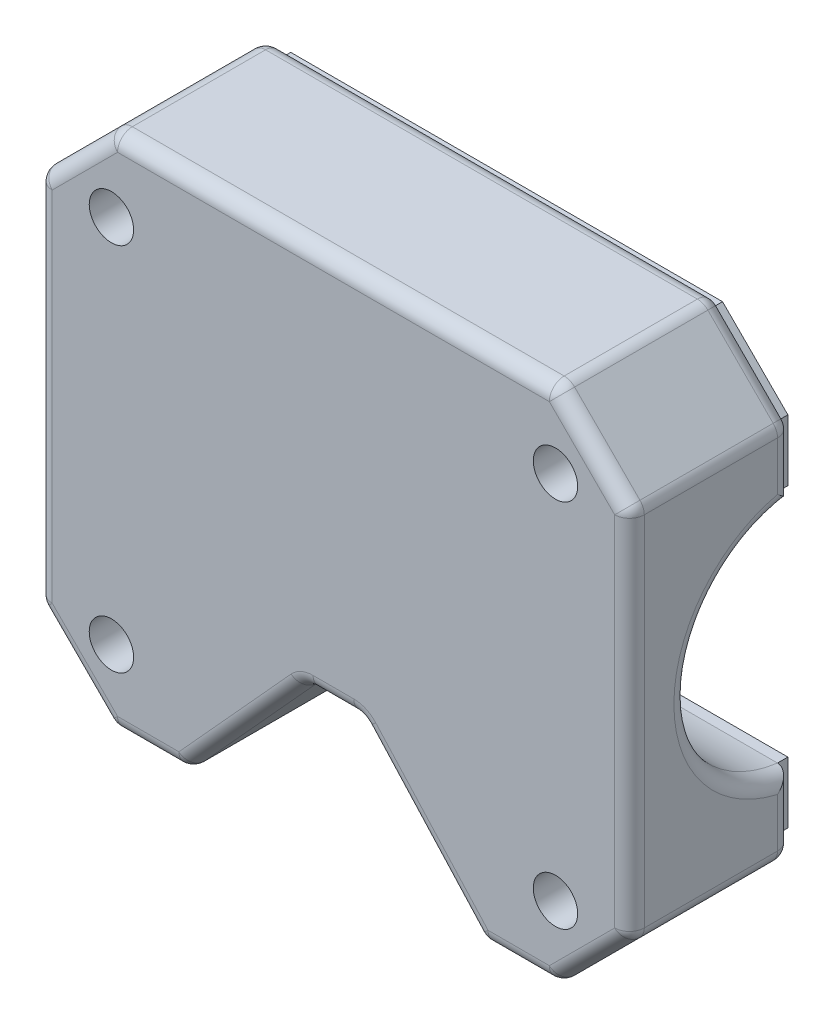
SolidWorks part; units mm, degrees
ref_plane "Front Plane" through (0, 0, 0) normal (0, 0, 1) x (1, 0, 0)
ref_plane "Top Plane" through (0, 0, 0) normal (0, 1, 0) x (1, 0, 0)
ref_plane "Right Plane" through (0, 0, 0) normal (1, 0, 0) x (0, 0, -1)
sketch "Sketch1" plane through (0, 0, 0) normal (0, 0, 1) x (1, 0, 0)
  line L1 (-20, -17.5) -> (20, -17.5)
  line L2 (-20, -17.5) -> (-20, 17.5)
  line L3 (-20, 17.5) -> (20, 17.5)
  line L4 (20, -17.5) -> (20, 17.5)
  line L5 (-20, -17.5) -> (20, 17.5) construction
  line L6 (-20, 17.5) -> (20, -17.5) construction
  line L7 (-15, -12.5) -> (15, -12.5) construction
  line L8 (-15, -12.5) -> (-15, 12.5) construction
  line L9 (-15, 12.5) -> (15, 12.5) construction
  line L10 (15, -12.5) -> (15, 12.5) construction
  line L11 (-15, -12.5) -> (15, 12.5) construction
  line L12 (-15, 12.5) -> (15, -12.5) construction
  circle A0 centre (0, 0) radius 8 construction
  circle A1 centre (-15, 12.5) radius 1.5
  circle A2 centre (15, 12.5) radius 1.5
  circle A3 centre (15, -12.5) radius 1.5
  circle A4 centre (-15, -12.5) radius 1.5
  dimension "D1" = 16
  dimension "D2" = 3
  dimension "D3" = 30
  dimension "D4" = 25
  dimension "D5" = 40
  dimension "D6" = 35
extrude "Boss-Extrude1" add sketch "Sketch1" along normal blind 12
sketch "Sketch2" plane through (-20, 0, 0) normal (-1, 0, 0) x (0, 0, 1)
  line L1 (1, 17.5) -> (1, -17.5)
  line L2 (1, 17.5) -> (1, -17.5)
  line L3 (1, 17.5) -> (1, -17.5)
  line L4 (1, 17.5) -> (29.851, 17.5)
  line L5 (1, -17.5) -> (29.851, -17.5)
  line L6 (29.851, 17.5) -> (29.851, -17.5)
  line L8 (1, 17.5) -> (0, 17.5)
  line L9 (1, 17.5) -> (1, -17.5)
  line L10 (1, -17.5) -> (0, -17.5)
  line L11 (0, 17.5) -> (0, -17.5)
  circle A0 centre (0, 0) radius 8
  line M5 (0, 17.5) -> (0, -17.5)
  line M6 (0, -17.5) -> (12, -17.5)
  line M8 (12, 17.5) -> (0, 17.5)
  dimension "D1" = 16
  dimension "D2" = 1
extrude "Cut-Extrude1" cut sketch "Sketch2" against normal blind 40 contours L9 A0 | L9 A0 L11 | A0 L1 M8 M5 | A0 L1 M5 M6 region at (-20, 12.7395, 0.5005) region at (-20, 0, 3.9418) region at (-20, 0, 0.4993) region at (-20, -12.7395, 0.5005)
sketch "Sketch5" plane through (0, 17.5, 0) normal (0, 1, 0) x (1, 0, 0)
  line L0 (-13.5, -4) -> (-13.5, -30.1703)
  line L1 (-13.5, -43.5797) -> (-13.5, -53)
  line L2 (-12.5, -54) -> (12.5, -54)
  line L3 (13.5, -53) -> (13.5, -43.5665)
  line L4 (13.5, -30.1671) -> (13.5, -4)
  line L5 (12.5, -3) -> (-12.5, -3)
  line L6 (0, -1) -> (0, -3)
  line L7 (20, -1) -> (-20, -1) construction
  line L8 (11, -53.75) -> (11, -36.875)
  line L9 (11, -36.875) -> (11, -20)
  line L10 (8, -17) -> (2.5, -17)
  line L11 (2.5, -17) -> (2.5, -12)
  line L12 (2.5, -12) -> (-2.5, -12)
  line L13 (-2.5, -12) -> (-2.5, -17)
  line L14 (-2.5, -17) -> (-8, -17)
  line L15 (-11, -20) -> (-11, -36.875)
  line L16 (-11, -36.875) -> (-11, -53.75)
  line L17 (-10.75, -54) -> (10.75, -54)
  circle A0 centre (-8.5, -48.5) radius 1.5
  arc A1 (-13.5, -53) -> (-12.5, -54) centre (-12.5, -53) ccw
  arc A2 (12.5, -54) -> (13.5, -53) centre (12.5, -53) ccw
  arc A3 (13.5, -4) -> (12.5, -3) centre (12.5, -4) ccw
  arc A4 (-12.5, -3) -> (-13.5, -4) centre (-12.5, -4) ccw
  circle A5 centre (8.5, -48.5) radius 1.5
  circle A6 centre (0, -14.5) radius 1.5
  circle A7 centre (0, -14.5) radius 1.5
  arc A8 (11, -20) -> (8, -17) centre (8, -20) ccw
  arc A9 (-8, -17) -> (-11, -20) centre (-8, -20) ccw
  arc A10 (-11, -53.75) -> (-10.75, -54) centre (-10.75, -53.75) ccw
  arc A11 (10.75, -54) -> (11, -53.75) centre (10.75, -53.75) ccw
  circle A12 centre (-8.5, -48.5) radius 1.5
  circle A13 centre (8.5, -48.5) radius 1.5
  spline S0 degree 3 poles (-13.5, -30.1703) (-13.5, -30.7241) (-13.4554, -31.2832) (-13.3208, -32.3903) (-13.2305, -32.9411) (-13.0479, -34.0426) (-12.9558, -34.5932) (-12.8189, -35.7001) (-12.7757, -36.2565) (-12.7724, -36.9579) (-12.7742, -37.1017) (-12.7828, -37.3864) (-12.7895, -37.5285) (-12.8164, -37.9539) (-12.8435, -38.2364) (-12.9441, -39.0815) (-13.037, -39.6418) (-13.2228, -40.7624) (-13.3155, -41.3227) (-13.454, -42.449) (-13.5, -43.016) (-13.5, -43.5797) knots 0 0 0 0 0.125 0.125 0.25 0.25 0.375 0.375 0.5 0.5 0.53125 0.53125 0.5625 0.5625 0.625 0.625 0.75 0.75 0.875 0.875 1 1 1 1
  spline S1 degree 3 poles (13.5, -43.5665) (13.5, -43.0131) (13.4554, -42.4545) (13.3209, -41.3482) (13.2307, -40.7978) (13.0482, -39.6971) (12.9562, -39.1469) (12.8195, -38.0409) (12.7762, -37.4849) (12.7729, -36.784) (12.7747, -36.6403) (12.7833, -36.3558) (12.79, -36.2138) (12.8169, -35.7887) (12.844, -35.5065) (12.9445, -34.662) (13.0373, -34.1021) (13.223, -32.9823) (13.3156, -32.4224) (13.454, -31.2969) (13.5, -30.7304) (13.5, -30.1671) knots 0 0 0 0 0.125 0.125 0.25 0.25 0.375 0.375 0.5 0.5 0.53125 0.53125 0.5625 0.5625 0.625 0.625 0.75 0.75 0.875 0.875 1 1 1 1
  point P28 (0, -3)
  dimension "D3" = 5
  dimension "D4" = 5.5
  dimension "D6" = 8.5
  dimension "D14" = 5.5
  dimension "D1" = 2
  dimension "D2" = 17
  dimension "D5" = 34
  dimension "D7" = 4.5
  dimension "D8" = 4
  dimension "D9" = 51
  dimension "D10" = 2.5
  dimension "D11" = 2.5
  dimension "D12" = 17
  dimension "D13" = 2.5
  dimension "D15" = 5.5
sketch "Sketch6" plane through (0, 17.5, 0) normal (0, 1, 0) x (1, 0, 0)
  line L0 (0, -1) -> (0, -3) construction
  line L1 (0, -1) -> (0, -3)
  line L2 (0, -13) -> (0, -16)
  line L3 (20.5345, -17) -> (11.5, -17)
  line L4 (3, -16.5) -> (3, -11.5)
  line L5 (3, -11.5) -> (-3, -11.5)
  line L6 (-20, -12) -> (20, -12)
  line L7 (20, -12) -> (20, -1)
  line L10 (-20, -12) -> (20, -12)
  line L11 (20, -12) -> (20, -1)
  line L12 (-3, -11.5) -> (-3, -16.5)
  line L13 (11.5, -12) -> (11.5, -36.875)
  line L14 (13.5, -30.1671) -> (13.5, -4)
  line L15 (13.5, -53) -> (13.5, -43.5665)
  line L16 (-12.5, -54) -> (12.5, -54)
  line L17 (-13.5, -43.5797) -> (-13.5, -53)
  line L18 (-13.5, -4) -> (-13.5, -30.1703)
  line L19 (12.5, -3) -> (-12.5, -3)
  line L20 (13.5, -30.1671) -> (13.5, -4)
  line L21 (13.5, -53) -> (13.5, -43.5665)
  line L22 (-12.5, -54) -> (12.5, -54)
  line L23 (-13.5, -43.5797) -> (-13.5, -53)
  line L24 (-13.5, -4) -> (-13.5, -30.1703)
  line L25 (12.5, -3) -> (-12.5, -3)
  line L26 (11.5, -36.875) -> (11.5, -16.5)
  line L27 (20.5345, -16.5) -> (2.5, -16.5)
  line L28 (20, -1) -> (-20, -1)
  line L29 (20, -1) -> (-20, -1)
  line L30 (-11, -36.875) -> (-11, -53.75)
  line L31 (-10.75, -54) -> (10.75, -54)
  line L32 (11, -53.75) -> (11, -36.875)
  line L33 (11, -36.875) -> (11, -20)
  line L34 (8, -17) -> (2.5, -17)
  line L35 (2.5, -17) -> (2.5, -12)
  line L36 (2.5, -12) -> (-2.5, -12)
  line L37 (-2.5, -12) -> (-2.5, -17)
  line L38 (-2.5, -17) -> (-8, -17)
  line L39 (-11, -20) -> (-11, -36.875)
  line L40 (-11, -36.875) -> (-11, -53.75) construction
  line L41 (-10.75, -54) -> (10.75, -54)
  line L42 (11, -53.75) -> (11, -36.875) construction
  line L43 (11, -36.875) -> (11, -17) construction
  line L44 (3, -17) -> (2.5, -17) construction
  line L45 (2.5, -16.5) -> (2.5, -12) construction
  line L46 (2.5, -12) -> (-2.5, -12) construction
  line L47 (-2.5, -12) -> (-2.5, -16.5) construction
  line L48 (-2.5, -17) -> (-3, -17) construction
  line L49 (-11, -17) -> (-11, -36.875) construction
  line L50 (-11.5, -16.5) -> (-11.5, -36.875)
  line L54 (-20, -1) -> (-20, -12)
  line L55 (-20, -1) -> (-20, -12)
  line L56 (-11.5, -36.875) -> (-11.5, -12)
  line L58 (-11.5, -17) -> (-11.5, -36.875) construction
  line L59 (11.5, -36.875) -> (11.5, -17) construction
  line L60 (8, -17) -> (3, -17) construction
  line L61 (3, -17) -> (2.5, -17) construction
  line L62 (20.5345, -17) -> (-20.5345, -17) construction
  line L63 (8, -17) -> (3, -17) construction
  line L64 (11, -17) -> (8, -17) construction
  line L65 (11.5, -17) -> (11, -17) construction
  line L66 (-8, -17) -> (-11, -17) construction
  line L67 (-11, -17) -> (-20.5345, -17)
  line L68 (-3, -17) -> (-8, -17) construction
  line L69 (-3, -17) -> (-8, -17) construction
  line L70 (-3, -16.5) -> (-3, -17) construction
  line L71 (-3, -11.5) -> (-3, -17) construction
  line L72 (-2.5, -16.5) -> (-2.5, -17) construction
  line L73 (-2.5, -12) -> (-2.5, -17) construction
  line L74 (0, -17) -> (-2.5, -17) construction
  line L75 (-2.5, -17) -> (-3, -17) construction
  line L76 (2.5, -17) -> (0, -17) construction
  line L77 (0, -16.5) -> (0, -17) construction
  line L78 (2.5, -17) -> (2.5, -16.5) construction
  line L79 (2.5, -17) -> (2.5, -12) construction
  line L80 (3, -17) -> (3, -16.5) construction
  line L81 (3, -17) -> (3, -11.5) construction
  line L82 (0, -16.5) -> (-2.5, -16.5) construction
  line L83 (-2.5, -16.5) -> (-20.5345, -16.5)
  line L84 (20.5345, -16.5) -> (-20.5345, -16.5) construction
  line L85 (2.5, -16.5) -> (0, -16.5) construction
  line L86 (0, -16) -> (0, -16.5) construction
  line L87 (-11.5, -36.875) -> (-11.5, -53.75) construction
  line L88 (11.5, -53.75) -> (11.5, -36.875) construction
  circle A1 centre (0, -14.5) radius 1.5
  circle A2 centre (0, -14.5) radius 1.5
  circle A3 centre (8.5, -48.5) radius 1.5
  circle A4 centre (8.5, -48.5) radius 1.5
  circle A5 centre (-8.5, -48.5) radius 1.5
  circle A6 centre (-8.5, -48.5) radius 1.5
  circle A7 centre (8.5, -48.5) radius 1.5
  circle A8 centre (8.5, -48.5) radius 1.5
  circle A9 centre (-8.5, -48.5) radius 1.5
  arc A10 (12.5, -54) -> (13.5, -53) centre (12.5, -53) ccw
  arc A11 (-13.5, -53) -> (-12.5, -54) centre (-12.5, -53) ccw
  arc A12 (-12.5, -3) -> (-13.5, -4) centre (-12.5, -4) ccw
  arc A13 (13.5, -4) -> (12.5, -3) centre (12.5, -4) ccw
  arc A14 (12.5, -54) -> (13.5, -53) centre (12.5, -53) ccw
  arc A15 (-13.5, -53) -> (-12.5, -54) centre (-12.5, -53) ccw
  arc A16 (-12.5, -3) -> (-13.5, -4) centre (-12.5, -4) ccw
  arc A17 (13.5, -4) -> (12.5, -3) centre (12.5, -4) ccw
  circle A18 centre (-8.5, -48.5) radius 1.5
  circle A19 centre (0, -14.5) radius 1.5
  circle A20 centre (0, -14.5) radius 1.5
  arc A24 (-11, -53.75) -> (-10.75, -54) centre (-10.75, -53.75) ccw
  arc A25 (10.75, -54) -> (11, -53.75) centre (10.75, -53.75) ccw
  arc A26 (11, -20) -> (8, -17) centre (8, -20) ccw
  arc A27 (-8, -17) -> (-11, -20) centre (-8, -20) ccw
  arc A28 (-11, -53.75) -> (-10.75, -54) centre (-10.75, -53.75) ccw
  arc A29 (10.75, -54) -> (11, -53.75) centre (10.75, -53.75) ccw
  spline S2 degree 3 poles (-1839.9896, 705.567) (-22.6944, -99.5408) (16.2779, -65.6646) (13.3209, -41.3482) (13.2307, -40.7978) (13.0482, -39.6971) (12.9562, -39.1469) (12.8195, -38.0409) (12.7762, -37.4849) (12.7729, -36.784) (12.7747, -36.6403) (12.7833, -36.3558) (12.79, -36.2138) (12.8169, -35.7887) (12.844, -35.5065) (12.9445, -34.662) (13.0373, -34.1021) (13.223, -32.9823) (13.3156, -32.4224) (16.3667, -7.6115) (-23.7373, 23.6583) (-1930.3468, -497.7988) knots -5.245055 -5.245055 -5.245055 -5.245055 0.125 0.125 0.25 0.25 0.375 0.375 0.5 0.5 0.53125 0.53125 0.5625 0.5625 0.625 0.625 0.75 0.75 0.875 0.875 6.261207 6.261207 6.261207 6.261207 only from (13.5, -43.5665) to (13.5, -30.1671)
  spline S3 degree 3 poles (1840.0279, -779.2675) (22.7021, 25.8288) (-16.2792, -8.0617) (-13.3208, -32.3903) (-13.2305, -32.9411) (-13.0479, -34.0426) (-12.9558, -34.5932) (-12.8189, -35.7001) (-12.7757, -36.2565) (-12.7724, -36.9579) (-12.7742, -37.1017) (-12.7828, -37.3864) (-12.7895, -37.5285) (-12.8164, -37.9539) (-12.8435, -38.2364) (-12.9441, -39.0815) (-13.037, -39.6418) (-13.2228, -40.7624) (-13.3155, -41.3227) (-16.368, -66.1456) (23.7438, -97.4284) (1930.2804, 423.9865) knots -5.243742 -5.243742 -5.243742 -5.243742 0.125 0.125 0.25 0.25 0.375 0.375 0.5 0.5 0.53125 0.53125 0.5625 0.5625 0.625 0.625 0.75 0.75 0.875 0.875 6.25979 6.25979 6.25979 6.25979 only from (-13.5, -30.1703) to (-13.5, -43.5797)
  spline S4 degree 3 poles (13.5, -43.5665) (13.5, -43.0131) (13.4554, -42.4545) (13.3209, -41.3482) (13.2307, -40.7978) (13.0482, -39.6971) (12.9562, -39.1469) (12.8195, -38.0409) (12.7762, -37.4849) (12.7729, -36.784) (12.7747, -36.6403) (12.7833, -36.3558) (12.79, -36.2138) (12.8169, -35.7887) (12.844, -35.5065) (12.9445, -34.662) (13.0373, -34.1021) (13.223, -32.9823) (13.3156, -32.4224) (13.454, -31.2969) (13.5, -30.7304) (13.5, -30.1671) knots 0 0 0 0 0.125 0.125 0.25 0.25 0.375 0.375 0.5 0.5 0.53125 0.53125 0.5625 0.5625 0.625 0.625 0.75 0.75 0.875 0.875 1 1 1 1
  spline S5 degree 3 poles (-13.5, -30.1703) (-13.5, -30.7241) (-13.4554, -31.2832) (-13.3208, -32.3903) (-13.2305, -32.9411) (-13.0479, -34.0426) (-12.9558, -34.5932) (-12.8189, -35.7001) (-12.7757, -36.2565) (-12.7724, -36.9579) (-12.7742, -37.1017) (-12.7828, -37.3864) (-12.7895, -37.5285) (-12.8164, -37.9539) (-12.8435, -38.2364) (-12.9441, -39.0815) (-13.037, -39.6418) (-13.2228, -40.7624) (-13.3155, -41.3227) (-13.454, -42.449) (-13.5, -43.016) (-13.5, -43.5797) knots 0 0 0 0 0.125 0.125 0.25 0.25 0.375 0.375 0.5 0.5 0.53125 0.53125 0.5625 0.5625 0.625 0.625 0.75 0.75 0.875 0.875 1 1 1 1
  point P55 (0, -14.5)
  point P61 (0, -17)
  dimension "D1" = 0
  dimension "D2" = 0
  dimension "D3" = 0
  dimension "D4" = 0
  dimension "D5" = 0
  dimension "D6" = 0
  dimension "D7" = 0
  dimension "D8" = 0
  dimension "D9" = 0
  dimension "D10" = 0.5
  dimension "D11" = 0.5
chamfer "Chamfer1" distance 5 angle 45 4 edges at (20, -17.5, 6.5) (-20, -17.5, 6.5) (20, 17.5, 6.5) (-20, 17.5, 6.5)
sketch "Sketch11" plane through (0, 0, 12) normal (0, 0, 1) x (1, 0, 0)
  line L0 (11.5, -6.5) -> (-11.5, -6.5)
  line L1 (0, -6.5) -> (-10, -17.5)
  line L2 (0, -6.5) -> (10, -17.5)
  line L3 (11.5, -8.5) -> (-11.5, -8.5)
  line L12 (-15, -17.5) -> (15, -17.5)
  line L13 (15, -17.5) -> (20, -12.5)
  line L14 (20, -12.5) -> (20, 12.5)
  line L15 (20, 12.5) -> (15, 17.5)
  line L16 (15, 17.5) -> (-15, 17.5)
  line L21 (-15, 17.5) -> (-20, 12.5)
  line L22 (-20, 12.5) -> (-20, -12.5)
  line L23 (-20, -12.5) -> (-15, -17.5)
  line L24 (-15, -17.5) -> (15, -17.5)
  line L25 (15, -17.5) -> (20, -12.5)
  line L26 (20, -12.5) -> (20, 12.5)
  line L27 (20, 12.5) -> (15, 17.5)
  line L28 (15, 17.5) -> (-15, 17.5)
  line L33 (-15, 17.5) -> (-20, 12.5)
  line L34 (-20, 12.5) -> (-20, -12.5)
  line L35 (-20, -12.5) -> (-15, -17.5)
  line M13 (-15, -17.5) -> (15, -17.5)
  dimension "D3" = 5
  dimension "D4" = 5
  dimension "D1" = 0
  dimension "D5" = 2
extrude "Cut-Extrude5" cut sketch "Sketch11" against normal blind 59 contours L2 L3 L1 M13 region at (0, -14.0385, 12)
fillet "Fillet2" radius 1 2 edges at (1.8182, -8.5, 6.5) (-1.8182, -8.5, 6.5)
fillet "Fillet3" radius 1 41 edges at (1.7804, -8.5855, 1) (-1.7804, -8.5855, 1) (1.7804, -8.5855, 12) (0, -8.5, 12) (-1.7804, -8.5855, 12) (6.0579, -13.1637, 1) (6.0579, -13.1637, 12) (-6.0579, -13.1637, 1) (-6.0579, -13.1637, 12) (17.5, -15, 1) (17.5, -15, 12) (-17.5, -15, 1) (-17.5, -15, 12) (-17.5, 15, 1) (-17.5, 15, 12) (17.5, 15, 1) (17.5, 15, 12) (0, 17.5, 12) (-15, 17.5, 6.5) (0, 17.5, 1) (15, 17.5, 6.5) (20, 12.5, 6.5) (20, 10.2186, 1) (20, 0, 8) (20, -10.2186, 1) (20, -12.5, 6.5) (20, 0, 12) (-20, 0, 8) (-20, 10.2186, 1) (-20, 12.5, 6.5) (-20, 0, 12) (-20, -12.5, 6.5) (-20, -10.2186, 1) (12.5, -17.5, 12) (15, -17.5, 6.5) (12.5, -17.5, 1) (10, -17.5, 6.5) (-12.5, -17.5, 1) (-15, -17.5, 6.5) (-12.5, -17.5, 12) (-10, -17.5, 6.5)
sketch "Sketch12" plane through (0, 0, 1) normal (0, 0, -1) x (-1, 0, 0)
  line L0 (-14.5858, 16.5) -> (-19, 12.0858) construction
  line L1 (-19, 12.0858) -> (-19, 7.9373) construction
  line L2 (-19, 7.9373) -> (19, 7.9373) construction
  line L3 (19, 7.9373) -> (19, 12.0858) construction
  line L4 (19, 12.0858) -> (14.5858, 16.5) construction
  line L5 (14.5858, 16.5) -> (-14.5858, 16.5) construction
  line L6 (14.5858, -16.5) -> (19, -12.0858) construction
  line L7 (19, -12.0858) -> (19, -7.9373) construction
  line L8 (19, -7.9373) -> (2.6239, -7.9373) construction
  line L9 (2.8557, -8.1547) -> (10.4424, -16.5) construction
  line L10 (10.4424, -16.5) -> (14.5858, -16.5) construction
  line L11 (-2.6239, -7.9373) -> (-19, -7.9373) construction
  line L12 (-19, -7.9373) -> (-19, -12.0858) construction
  line L13 (-19, -12.0858) -> (-14.5858, -16.5) construction
  line L14 (-14.5858, -16.5) -> (-10.4424, -16.5) construction
  line L15 (-10.4424, -16.5) -> (-2.8557, -8.1547) construction
  line L16 (-14.5858, 16.5) -> (-19, 12.0858)
  line L17 (-19, 12.0858) -> (-19, 7.9373)
  line L18 (-19, 7.9373) -> (19, 7.9373)
  line L19 (19, 7.9373) -> (19, 12.0858)
  line L20 (19, 12.0858) -> (14.5858, 16.5)
  line L21 (14.5858, 16.5) -> (-14.5858, 16.5)
  line L22 (14.5858, -16.5) -> (19, -12.0858)
  line L23 (19, -12.0858) -> (19, -7.9373)
  line L24 (19, -7.9373) -> (2.6239, -7.9373)
  line L25 (2.8557, -8.1547) -> (10.4424, -16.5)
  line L26 (10.4424, -16.5) -> (14.5858, -16.5)
  line L27 (-2.6239, -7.9373) -> (-19, -7.9373)
  line L28 (-19, -7.9373) -> (-19, -12.0858)
  line L29 (-19, -12.0858) -> (-14.5858, -16.5)
  line L30 (-14.5858, -16.5) -> (-10.4424, -16.5)
  line L31 (-10.4424, -16.5) -> (-2.8557, -8.1547)
  arc A0 (2.8557, -8.1547) -> (2.6239, -7.9373) centre (1.3758, -9.5) ccw construction
  arc A1 (-2.6239, -7.9373) -> (-2.8557, -8.1547) centre (-1.3758, -9.5) ccw construction
  circle A2 centre (15, 12.5) radius 1.5 construction
  circle A3 centre (-15, 12.5) radius 1.5 construction
  circle A4 centre (-15, -12.5) radius 1.5 construction
  circle A5 centre (15, -12.5) radius 1.5 construction
  arc A6 (2.8557, -8.1547) -> (2.6239, -7.9373) centre (1.3758, -9.5) ccw
  arc A7 (-2.6239, -7.9373) -> (-2.8557, -8.1547) centre (-1.3758, -9.5) ccw
  circle A8 centre (15, 12.5) radius 1.5
  circle A9 centre (-15, 12.5) radius 1.5
  circle A10 centre (-15, -12.5) radius 1.5
  circle A11 centre (15, -12.5) radius 1.5
extrude "Boss-Extrude2" add sketch "Sketch12" along normal blind 0.7 contours L27 L28 L29 L30 L31 A7 | L16 L17 L18 L19 L20 L21 | L22 L23 L24 A6 L25 L26
